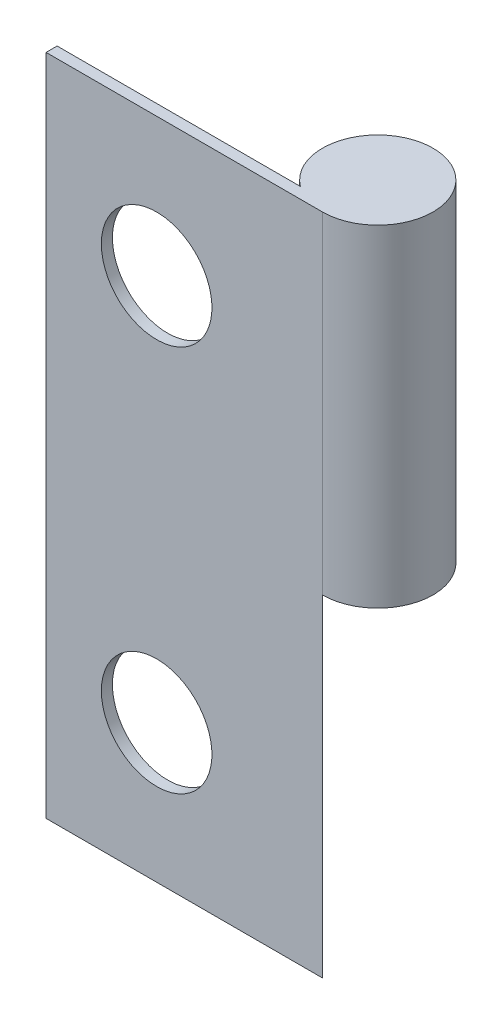
SolidWorks part; units mm, degrees
ref_plane "Front Plane" through (0, 0, 0) normal (0, 0, 1) x (1, 0, 0)
ref_plane "Top Plane" through (0, 0, 0) normal (0, 1, 0) x (1, 0, 0)
ref_plane "Right Plane" through (0, 0, 0) normal (1, 0, 0) x (0, 0, -1)
sketch "Sketch1" plane through (0, 0, 0) normal (0, 1, 0) x (1, 0, 0)
  line L0 (0, 0.3175) -> (0, 0)
  line L1 (0, 0) -> (-7.9375, 0)
  line L4 (-7.9375, 0) -> (-7.9375, 0.3175)
  line L5 (-7.9375, 0.3175) -> (0, 0.3175)
  circle A0 centre (0, 1.5875) radius 1.5875
  point P7 (0, 0)
  point P8 (-1.5875, 1.5875)
  point P9 (-1.2342, 1.8731)
  point P10 (0, 0)
  point P11 (0, 0)
  point P12 (0, 0)
  dimension "D1" = 6.35
  dimension "D2" = 3.175
  dimension "D3" = 0.3175
extrude "Boss-Extrude1" add sketch "Sketch1" along normal blind 19.05 contours A0 L4 L1 | A0 | A0 region at (0.0097, 0, -1.6249) region at (-0.3625, 0, -0.1893) region at (-4.2898, 0, -0.156)
extrude "Cut-Extrude2" cut sketch "Sketch1<4>" along normal blind 9.525 contours A0 | A0 region at (0.0097, 0, -1.6249) region at (-0.3625, 0, -0.1893)
sketch "Sketch1<4>" plane through (0, 0, 0) normal (0, 1, 0) x (1, 0, 0) same geometry as "Sketch1"
sketch "Sketch2" plane through (0, 0, -0.3175) normal (0, 0, -1) x (-1, 0, 0)
  line L0 (4.7625, 15.0813) -> (4.7625, 3.9688) construction
  line L1 (7.9375, 19.05) -> (1.5875, 19.05) construction
  line L2 (7.9375, 19.05) -> (7.9375, 0) construction
  line L3 (7.9375, 0) -> (1.5875, 0) construction
  line L4 (1.5875, 19.05) -> (1.5875, 0) construction
  line L5 (1.5875, 9.525) -> (1.5875, 19.05) construction
  line L6 (1.5875, 19.05) -> (-1.5875, 19.05) construction
  circle A0 centre (4.7625, 15.0813) radius 1.5875
  circle A1 centre (4.7625, 3.9688) radius 1.5875
  point P10 (4.7625, 9.525)
  point P11 (4.7625, 19.05)
  point P12 (7.9375, 9.525)
  point P13 (0, 0)
  point P14 (0, 0)
  point P15 (0, 0)
  point P16 (7.9375, 0)
  point P18 (7.9375, 19.05)
  point P20 (1.5875, 19.05)
  dimension "D1" = 11.1125
  dimension "D2" = 3.175
extrude "Cut-Extrude3" cut sketch "Sketch2" against normal through all
